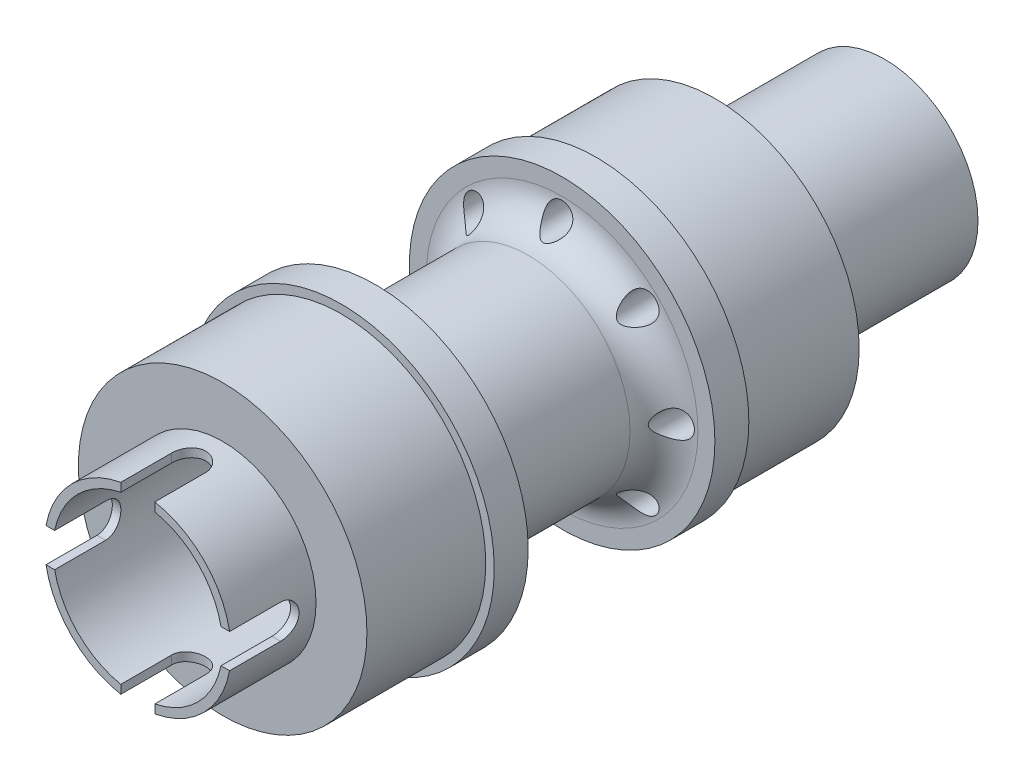
SolidWorks part; units mm, degrees
material "Alliage 1060"
ref_plane "Plan de face" through (0, 0, 0) normal (0, 0, 1) x (1, 0, 0)
ref_plane "Plan de dessus" through (0, 0, 0) normal (0, 1, 0) x (1, 0, 0)
ref_plane "Plan de droite" through (0, 0, 0) normal (1, 0, 0) x (0, 0, -1)
sketch "Esquisse1" plane through (0, 0, 0) normal (0, 0, 1) x (1, 0, 0)
  circle A0 centre (0, 0) radius 4.5
  circle A1 centre (0, 0) radius 5.5
  dimension "D1" = 9
  dimension "D2" = 11
extrude "Boss.-Extru.1" add sketch "Esquisse1" along normal blind 10
sketch "Esquisse3" plane through (0, 0, 10) normal (0, 0, 1) x (1, 0, 0)
  circle A0 centre (0, 0) radius 8.5
  circle A1 centre (0, 0) radius 5
  dimension "D1" = 10
  dimension "D2" = 17
extrude "Boss.-Extru.3" add sketch "Esquisse3" along normal blind 7
sketch "Esquisse4" plane through (0, 0, 17) normal (0, 0, 1) x (1, 0, 0)
  circle A0 centre (0, 0) radius 5
  circle A1 centre (0, 0) radius 9
  dimension "D1" = 10
  dimension "D2" = 18
extrude "Boss.-Extru.4" add sketch "Esquisse4" along normal blind 2
sketch "Esquisse7" plane through (0, 0, 19) normal (0, 0, 1) x (1, 0, 0)
  circle A0 centre (0, 0) radius 5
  circle A1 centre (0, 0) radius 6
  dimension "D1" = 10
  dimension "D2" = 12
extrude "Boss.-Extru.7" add sketch "Esquisse7" along normal blind 11
sketch "Esquisse8" plane through (0, 0, 30) normal (0, 0, 1) x (1, 0, 0)
  circle A0 centre (0, 0) radius 5
  circle A1 centre (0, 0) radius 9
  dimension "D1" = 10
  dimension "D2" = 18
extrude "Boss.-Extru.8" add sketch "Esquisse8" along normal blind 2
sketch "Esquisse15" plane through (0, 0, 32) normal (0, 0, 1) x (1, 0, 0)
  circle A0 centre (0, 0) radius 5
  circle A1 centre (0, 0) radius 8.5
  dimension "D1" = 10
  dimension "D2" = 17
extrude "Boss.-Extru.9" add sketch "Esquisse15" along normal blind 7
sketch "Esquisse16" plane through (0, 0, 39) normal (0, 0, 1) x (1, 0, 0)
  circle A0 centre (0, 0) radius 5
  circle A1 centre (0, 0) radius 5.5
  dimension "D1" = 10
  dimension "D2" = 11
extrude "Boss.-Extru.10" add sketch "Esquisse16" along normal blind 5
sketch "Esquisse17" plane through (0, 0, 44) normal (0, 0, 1) x (1, 0, 0)
  line L1 (-10, 1) -> (10, 1)
  line L2 (-10, 1) -> (-10, -1)
  line L3 (-10, -1) -> (10, -1)
  line L4 (10, 1) -> (10, -1)
  line L5 (-1, -10) -> (1, -10)
  line L6 (-1, -10) -> (-1, 10)
  line L7 (-1, 10) -> (1, 10)
  line L8 (1, -10) -> (1, 10)
  dimension "D1" = 2
  dimension "D2" = 1
  dimension "D3" = 10
  dimension "D4" = 20
  dimension "D5" = 2
  dimension "D6" = 20
  dimension "D7" = 10
  dimension "D8" = 1
extrude "Enlèv. mat.-Extru.1" cut sketch "Esquisse17" against normal blind 4 contours L6 L7 L8 L5 | L1 L4 L3 L2
hole_wizard "Trou pour taraudage pour trou taraudé M21" positions "Esquisse21" profile "Esquisse22" hole size "M2" standard "ISO" end condition up to next
sketch "Esquisse21" plane through (0, 0, 10) normal (0, 0, -1) x (-1, 0, 0)
  point P0 (-7, 0)
  point P11 (-4.9497, 4.9497)
  point P12 (0, 7)
  point P13 (4.9497, 4.9497)
  point P14 (7, 0)
  point P15 (4.9497, -4.9497)
  point P16 (0, -7)
  point P17 (-4.9497, -4.9497)
  point P18 (0, 0)
  dimension "D1" = 7
  dimension "D2" = 8
sketch "Esquisse22" plane through (7, 0, 10) normal (1, 0, 0) x (0, 1, 0)
  line L0 (0, 0) -> (0, 9)
  line L1 (0, 9) -> (0.8, 9)
  line L2 (0.8, 9) -> (0.8, 0)
  line L5 (0.8, 0) -> (0, 0)
  line L11 (0, -6.35) -> (0, 107.95) construction
  dimension "Diamètre du perçage jusqu'au prochain" = 1.6
  dimension "Profondeur du perçage jusqu'au prochain" = 9
fillet "Congé1" radius 2 2 edges at (6, 0, 19) (6, 0, 30)
fillet "Congé5" radius 1 4 edges at (0, -5.5, 40) (1, -5.1537, 40) (-1, -5.1537, 40) (0, -5, 40)
fillet "Congé6" radius 1 4 edges at (5.5, 0, 40) (5, 0, 40) (5.1537, 1, 40) (5.1537, -1, 40)
fillet "Congé7" radius 1 4 edges at (0, 5.5, 40) (0, 5, 40) (-1, 5.1537, 40) (1, 5.1537, 40)
fillet "Congé8" radius 1 4 edges at (-5.5, 0, 40) (-5.1537, 1, 40) (-5, 0, 40) (-5.1537, -1, 40)
